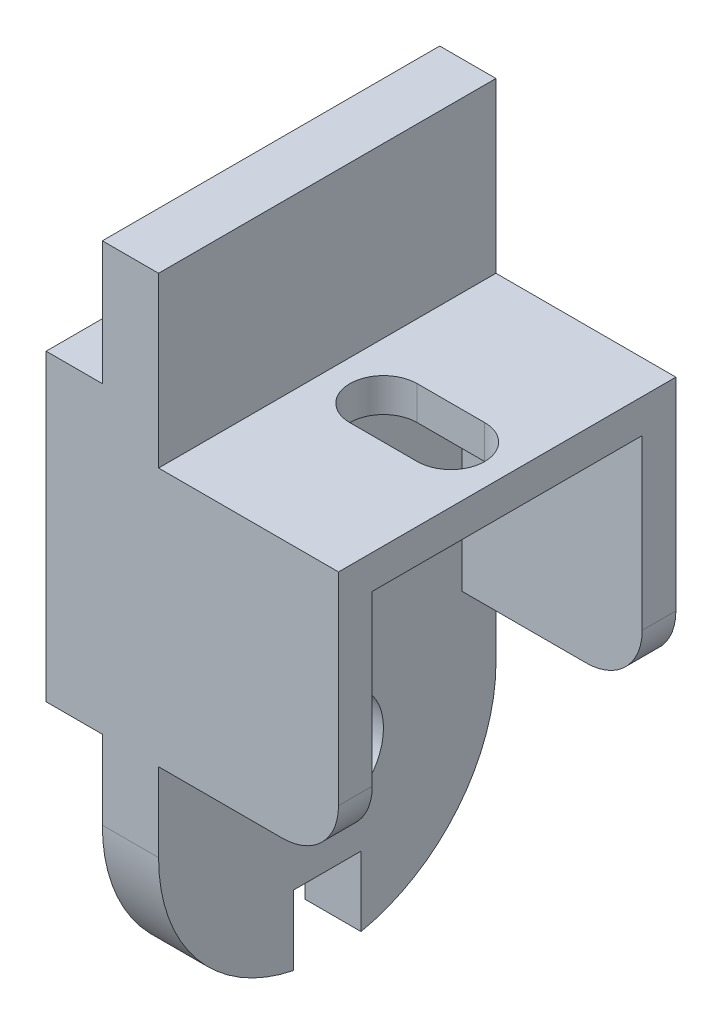
SolidWorks part; units mm, degrees
ref_plane "Спереди" through (0, 0, 0) normal (0, 0, 1) x (1, 0, 0)
ref_plane "Сверху" through (0, 0, 0) normal (0, 1, 0) x (1, 0, 0)
ref_plane "Справа" through (0, 0, 0) normal (1, 0, 0) x (0, 0, -1)
sketch "Эскиз1" plane through (0, 0, 0) normal (1, 0, 0) x (0, 0, -1)
  line L0 (0, 0) -> (0, 30) construction
  line L1 (-15, 0) -> (-15, 30)
  line L2 (15, 0) -> (15, 30)
  line L3 (-15, 30) -> (15, 30)
  line L4 (-3, -21.5) -> (3, -21.5)
  line L5 (-3, -21.5) -> (-3, -8.5)
  line L6 (-3, -8.5) -> (3, -8.5)
  line L7 (3, -21.5) -> (3, -8.5)
  line L8 (-3, -21.5) -> (3, -8.5) construction
  line L9 (-3, -8.5) -> (3, -21.5) construction
  line L10 (-15, 7) -> (-12, 7)
  line L11 (-12, 7) -> (-12, 27)
  line L12 (-12, 27) -> (12, 27)
  line L13 (12, 27) -> (12, 7)
  line L14 (12, 7) -> (15, 7)
  line L15 (-15, 30) -> (-15, 45)
  line L16 (-15, 45) -> (15, 45)
  line L17 (15, 45) -> (15, 30)
  arc A0 (-15, 0) -> (15, 0) centre (0, 0) ccw
  arc A1 (15, 30) -> (-15, 30) centre (0, 30) ccw
  circle A2 centre (0, 0) radius 5
  point P3 (0, 15)
  point P10 (0, -15)
  dimension "D3" = 10
  dimension "D1" = 30
  dimension "D2" = 30
  dimension "D4" = 13
  dimension "D5" = 6
  dimension "D6" = 23
  dimension "D7" = 3
  dimension "D8" = 3
extrude "Бобышка-Вытянуть1" add sketch "Эскиз1" along normal blind 5 contours L3 A1 | A1 L16 L15 | A1 L17 L16 | L1 A0 L5 L6 L7 L2 L14 L13 L12 L11 L10 A2 | L13 L14 L2 L3 L1 L10 L11 L12 region at (0, 7.6571, 0) region at (0, 18.5, 14.622) region at (0, 36.3662, 0) region at (0, 41.6495, 11.6495) region at (0, 41.6495, -11.6495)
extrude "Бобышка-Вытянуть2" add sketch "Эскиз1<4>" along normal blind 21 contours L13 L14 L2 L3 L1 L10 L11 L12 region at (0, 18.5, 14.622)
sketch "Эскиз1<4>" plane through (0, 0, 0) normal (1, 0, 0) x (0, 0, -1) same geometry as "Эскиз1"
fillet "Скругление1" radius 5 2 edges at (21, 7, 13.5) (21, 7, -13.5)
sketch "Эскиз3" plane through (0, 0, 0) normal (-1, 0, 0) x (0, 0, 1)
  line L0 (-15, 45) -> (-15, 0) construction
  line L1 (-15, 7) -> (15, 7)
  line L2 (-15, 7) -> (-15, 34)
  line L3 (-15, 34) -> (15, 34)
  line L4 (15, 7) -> (15, 34)
  line L5 (15, 0) -> (15, 45) construction
  line L6 (-15, 7) -> (-12, 7) construction
  dimension "D1" = 27
extrude "Бобышка-Вытянуть3" add sketch "Эскиз3" along normal blind 5
sketch "Эскиз4" plane through (0, 27, 0) normal (0, -1, 0) x (1, 0, 0)
  line L0 (5, 0) -> (21, 0) construction
  line L1 (5, -12) -> (5, 12) construction
  line L2 (21, 12) -> (21, -12) construction
  line L3 (10, 0) -> (16, 0) construction
  line L4 (10, 3) -> (16, 3)
  line L5 (10, -3) -> (16, -3)
  arc A0 (10, 3) -> (10, -3) centre (10, 0) ccw
  arc A1 (16, -3) -> (16, 3) centre (16, 0) ccw
  point P8 (13, 0)
  dimension "D2" = 6
  dimension "D1" = 6
extrude "Вырез-Вытянуть1" cut sketch "Эскиз4" against normal through all
